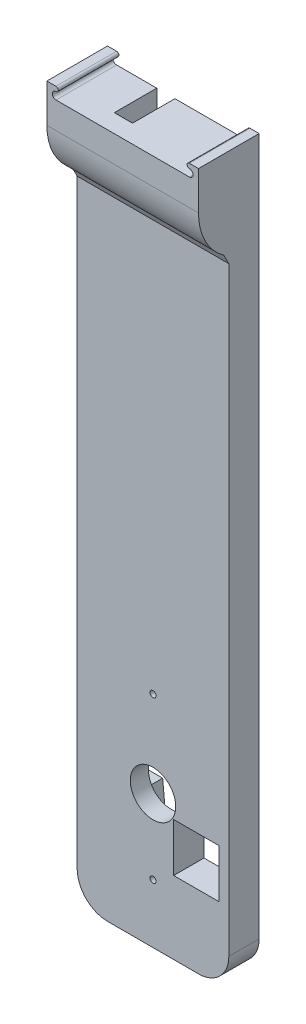
SolidWorks part; units mm, degrees
ref_plane "Přední rovina" through (0, 0, 0) normal (0, 0, 1) x (1, 0, 0)
ref_plane "Horní rovina" through (0, 0, 0) normal (0, 1, 0) x (1, 0, 0)
ref_plane "Pravá rovina" through (0, 0, 0) normal (1, 0, 0) x (0, 0, -1)
sketch "Skica1" plane through (0, 0, 0) normal (0, 0, 1) x (1, 0, 0)
  line L1 (0, 0) -> (25, 0)
  line L2 (0, 0) -> (0, 120)
  line L3 (0, 120) -> (25, 120)
  line L4 (25, 0) -> (25, 120)
  dimension "D1" = 120
  dimension "D2" = 25
extrude "Přidat vysunutím1" add sketch "Skica1" along normal blind 5
sketch "Skica2" plane through (0, 0, 0) normal (0, 0, -1) x (-1, 0, 0)
  line L0 (0, 120) -> (0, 0) construction
  line L1 (-25, 120) -> (0, 120)
  line L2 (-25, 120) -> (-25, 105)
  line L3 (-25, 105) -> (0, 105)
  line L4 (0, 120) -> (0, 105)
  dimension "D1" = 15
extrude "Přidat vysunutím2" add sketch "Skica2" against normal blind 10
fillet "Zaoblit5" radius 5 1 edges at (25, 0, 2.5)
fillet "Zaoblit6" radius 5 1 edges at (0, 0, 2.5)
sketch "Skica3" plane through (0, 0, 10) normal (0, 0, 1) x (1, 0, 0)
  line L0 (1.5, 118.04) -> (23.5, 118.04)
  line L1 (0, 120) -> (25, 120) construction
  line L4 (1.5, 120) -> (23.5, 120)
  line L5 (0, 105) -> (0, 120) construction
  line L6 (25, 120) -> (25, 105) construction
  arc A0 (23.5, 118.04) -> (23.5, 119.24) centre (23.5, 118.64) ccw
  arc A1 (23.5, 119.24) -> (23.5, 120) centre (23.5, 119.62) cw
  arc A2 (1.5, 118.04) -> (1.5, 119.24) centre (1.5, 118.64) cw
  arc A3 (1.5, 119.24) -> (1.5, 120) centre (1.5, 119.62) ccw
  dimension "D1" = 0.6
  dimension "D2" = 0.6
  dimension "D3" = 0.38
  dimension "D4" = 0.38
  dimension "D5" = 1.5
  dimension "D6" = 1.5
  dimension "D7" = 1.96
extrude "Odebrat vysunutím2" cut sketch "Skica3" against normal blind 20
fillet "Zaoblit7" radius 10 1 edges at (12.5, 105, 10)
fillet "Zaoblit8" radius 2 1 edges at (12.5, 105, 5) profile chamfer
sketch "Skica4" plane through (0, 118.04, 0) normal (0, 1, 0) x (1, 0, 0)
  line L0 (1.5, 0) -> (23.5, 0) construction
  line L1 (8.12, 0) -> (11.12, 0)
  line L2 (8.12, 0) -> (8.12, -7)
  line L3 (8.12, -7) -> (11.12, -7)
  line L4 (11.12, 0) -> (11.12, -7)
  line L5 (23.12, 0) -> (23.12, -10) construction
  dimension "D1" = 0
  dimension "D2" = 7
  dimension "D3" = 3
  dimension "D4" = 12
extrude "Odebrat vysunutím3" cut sketch "Skica4" against normal blind 4
sketch "Skica5" plane through (0, 0, 0) normal (0, 0, 1) x (1, 0, 0)
  line L0 (9, 21) -> (16, 21)
  line L1 (16, 21) -> (14, 43)
  line L3 (11, 43) -> (9, 21)
  line L4 (11, 43) -> (14, 43)
  line L5 (9, 21) -> (10.5, 5)
  line L6 (10.5, 5) -> (14.5, 5)
  line L7 (14.5, 5) -> (16, 21)
  line L9 (5, 0) -> (20, 0) construction
  line L10 (5.5, 24) -> (19.5, 24)
  line L11 (5.5, 24) -> (5.5, 20)
  line L12 (5.5, 20) -> (19.5, 20)
  line L13 (19.5, 24) -> (19.5, 20)
  arc A0 (5.5, 24) -> (5.5, 20) centre (5.5, 22) ccw
  arc A1 (19.5, 24) -> (19.5, 20) centre (19.5, 22) cw
  point P2 (12.5, 43)
  point P5 (12.5, 21)
  point P6 (12.5, 5)
  point P11 (12.5, 0)
  point P16 (12.5, 24)
  dimension "D1" = 7
  dimension "D2" = 3
  dimension "D3" = 22
  dimension "D4" = 16
  dimension "D5" = 5
  dimension "D6" = 4
  dimension "D7" = 19
  dimension "D8" = 14
  dimension "D9" = 4
extrude "Odebrat vysunutím4" cut sketch "Skica5" along normal blind 2 contours L3 L10 L1 L4 | L11 A0 | L11 L12 L5 L3 L10 | L10 L3 L0 L1 | L5 L12 L7 L0 | L13 L10 L1 L7 L12 | A1 L13 | L12 L5 L6 L7 region at (12.5, 22.4797, 0) region at (7.3079, 22.0229, 0) region at (12.5, 20.5023, 0) region at (17.6921, 22.0229, 0) region at (12.5, 32.3429, 0) region at (12.5, 13.1503, 0) region at (4.6512, 22, 0) region at (20.3488, 22, 0)
sketch "Skica7" plane through (0, 0, 2) normal (0, 0, -1) x (-1, 0, 0)
  line L0 (-11, 43) -> (-14, 43) construction
  line L1 (-21.5, 22) -> (-3.5, 22) construction
  circle A0 centre (-12.5, 36.2) radius 0.5
  circle A1 centre (-12.5, 9.7) radius 0.5
  arc A2 (-19.5, 24) -> (-19.5, 20) centre (-19.5, 22) ccw construction
  arc A3 (-5.5, 20) -> (-5.5, 24) centre (-5.5, 22) ccw construction
  point P9 (-12.5, 43)
  dimension "D1" = 1
  dimension "D2" = 1
  dimension "D4" = 12.3
  dimension "D3" = 14.2
extrude "Odebrat vysunutím5" cut sketch "Skica7" along normal offset from surface (2.8 mm away) 0.2 from surface up to face at (12.5, 22.6667, 2) starting at face at (12.5, 35.9593, 5)
sketch "Skica8" plane through (0, 0, 2) normal (0, 0, -1) x (-1, 0, 0)
  line L0 (-12.5, 43) -> (-12.5, 5) construction
  line L1 (-11, 43) -> (-14, 43) construction
  line L2 (-10.5, 5) -> (-14.5, 5) construction
  line L3 (-21.5, 22) -> (-3.5, 22) construction
  circle A0 centre (-12.5, 22) radius 3.75
  arc A1 (-19.5, 24) -> (-19.5, 20) centre (-19.5, 22) ccw construction
  arc A2 (-5.5, 20) -> (-5.5, 24) centre (-5.5, 22) ccw construction
  dimension "D3" = 7.5
  dimension "D1" = 0
  dimension "D2" = 0
extrude "Odebrat vysunutím6" cut sketch "Skica8" against normal through all
sketch "Skica9" plane through (0, 0, 0) normal (0, 0, -1) x (-1, 0, 0)
  line L1 (-15.9062, 20) -> (-23.4063, 20)
  line L2 (-15.9062, 20) -> (-15.9062, 12)
  line L3 (-15.9062, 12) -> (-23.4062, 12)
  line L4 (-23.4063, 20) -> (-23.4062, 12)
  dimension "D1" = 7.5
  dimension "D2" = 8
extrude "Odebrat vysunutím7" cut sketch "Skica9" against normal through all
